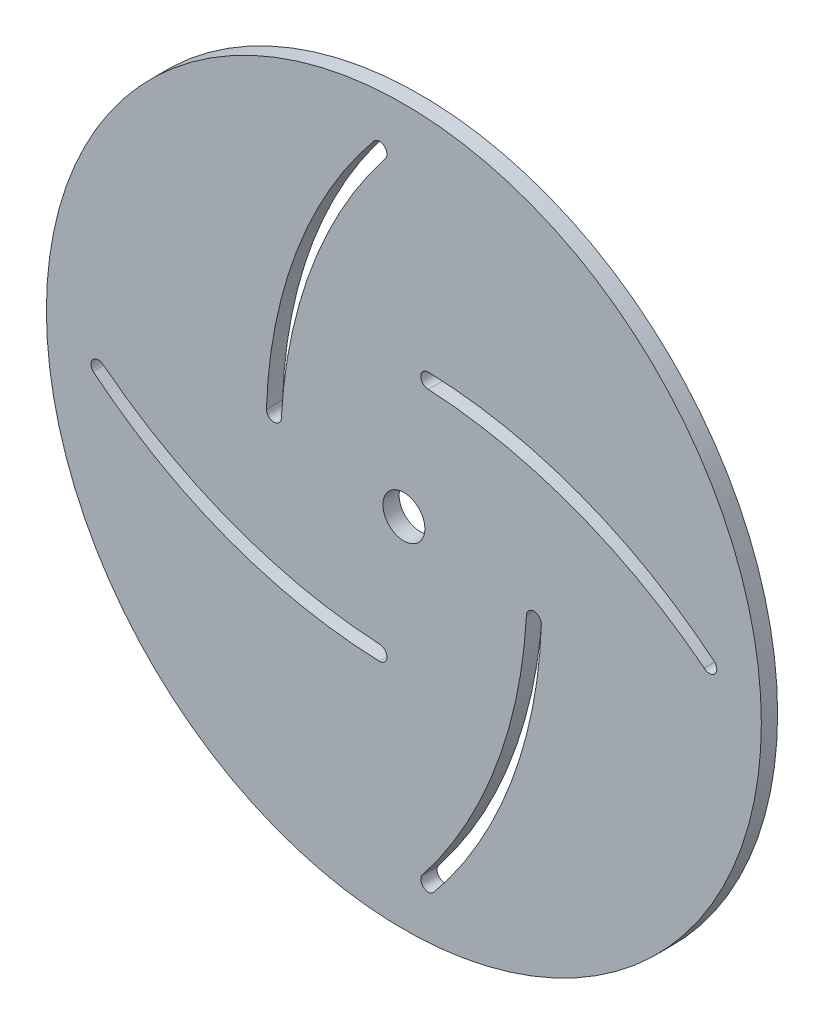
SolidWorks part; units mm, degrees
ref_plane "Front Plane" through (0, 0, 0) normal (0, 0, 1) x (1, 0, 0)
ref_plane "Top Plane" through (0, 0, 0) normal (0, 1, 0) x (1, 0, 0)
ref_plane "Right Plane" through (0, 0, 0) normal (1, 0, 0) x (0, 0, -1)
sketch "Sketch1" plane through (0, 0, 0) normal (0, 0, 1) x (1, 0, 0)
  line L0 (0, 0) -> (0, 69.85) construction
  line L1 (0, 69.85) -> (23.1636, 62.7607) construction
  line L2 (0, 0) -> (-69.85, 0) construction
  line L3 (-4.7625, 59.69) -> (-5.7884, 60.7159) construction
  line L4 (-4.7625, 59.69) -> (-3.7366, 58.6641) construction
  circle A13 centre (0, 0) radius 69.85
  circle A14 centre (0, 0) radius 4.1
  arc A42 (60.7159, 5.7884) -> (4.7776, 26.8568) centre (1.726, -66.0401) ccw
  arc A43 (4.7776, 26.8568) -> (4.7625, 23.943) centre (4.7625, 25.3999) ccw
  arc A44 (4.7625, 23.943) -> (58.6641, 3.7366) centre (-0.38, -71.7708) cw
  arc A46 (60.7159, 5.7884) -> (58.6641, 3.7366) centre (59.69, 4.7625) cw
  arc A47 (-23.943, 4.7625) -> (-3.7366, 58.6641) centre (71.7708, -0.38) cw
  arc A48 (-5.7884, 60.7159) -> (-26.8568, 4.7776) centre (66.0401, 1.726) ccw
  arc A50 (-26.8568, 4.7776) -> (-23.943, 4.7625) centre (-25.3999, 4.7625) ccw
  arc A51 (-5.7884, 60.7159) -> (-3.7366, 58.6641) centre (-4.7625, 59.69) cw
  arc A52 (5.7884, -60.7159) -> (26.8568, -4.7776) centre (-66.0401, -1.726) ccw
  arc A53 (26.8568, -4.7776) -> (23.943, -4.7625) centre (25.3999, -4.7625) ccw
  arc A54 (23.943, -4.7625) -> (3.7366, -58.6641) centre (-71.7708, 0.38) cw
  arc A55 (5.7884, -60.7159) -> (3.7366, -58.6641) centre (4.7625, -59.69) cw
  arc A56 (-60.7159, -5.7884) -> (-4.7776, -26.8568) centre (-1.726, 66.0401) ccw
  arc A57 (-4.7776, -26.8568) -> (-4.7625, -23.943) centre (-4.7625, -25.3999) ccw
  arc A58 (-4.7625, -23.943) -> (-58.6641, -3.7366) centre (0.38, 71.7708) cw
  arc A59 (-60.7159, -5.7884) -> (-58.6641, -3.7366) centre (-59.69, -4.7625) cw
  point P43 (0, 0)
  dimension "D1" = 59.69
  dimension "D2" = 4.7625
  dimension "D3" = 4
extrude "Boss-Extrude1" add sketch "Sketch1" along normal blind 3.175
sketch "Sketch2" plane through (0, 0, 3.175) normal (0, 0, 1) x (1, 0, 0)
  arc A0 (-25.3999, 4.7625) -> (-4.7625, 59.69) centre (66.5458, 1.5573) cw
sketch "Sketch3" plane through (0, 0, 3.175) normal (0, 0, 1) x (1, 0, 0)
  line L0 (-30.1624, 4.7625) -> (-65.0875, 4.7625)
  line L1 (4.7625, 30.1624) -> (4.7625, 65.0875)
  line L2 (30.1624, -4.7625) -> (65.0875, -4.7625)
  line L3 (-4.7625, -30.1624) -> (-4.7625, -65.0875)
  arc A1 (-65.0875, 4.7625) -> (-9.525, 65.0875) centre (0.5141, 0.0905) cw
  arc A2 (-30.1624, 4.7625) -> (-9.525, 65.0875) centre (45.0213, 12.7344) cw
  arc A3 (4.7625, 30.1624) -> (65.0875, 9.525) centre (12.7344, -45.0213) cw
  arc A4 (4.7625, 65.0875) -> (65.0875, 9.525) centre (0.0905, -0.5141) cw
  arc A5 (30.1624, -4.7625) -> (9.525, -65.0875) centre (-45.0213, -12.7344) cw
  arc A6 (65.0875, -4.7625) -> (9.525, -65.0875) centre (-0.5141, -0.0905) cw
  arc A7 (-4.7625, -30.1624) -> (-65.0875, -9.525) centre (-12.7344, 45.0213) cw
  arc A8 (-4.7625, -65.0875) -> (-65.0875, -9.525) centre (-0.0905, 0.5141) cw
  point P26 (0, 0)
  dimension "D2" = 4.7625
  dimension "D3" = 4
  dimension "D1" = 4.7625
  dimension "D4" = 4.7625
  dimension "D5" = 4.7625
equation "\"D\"= 6in"
